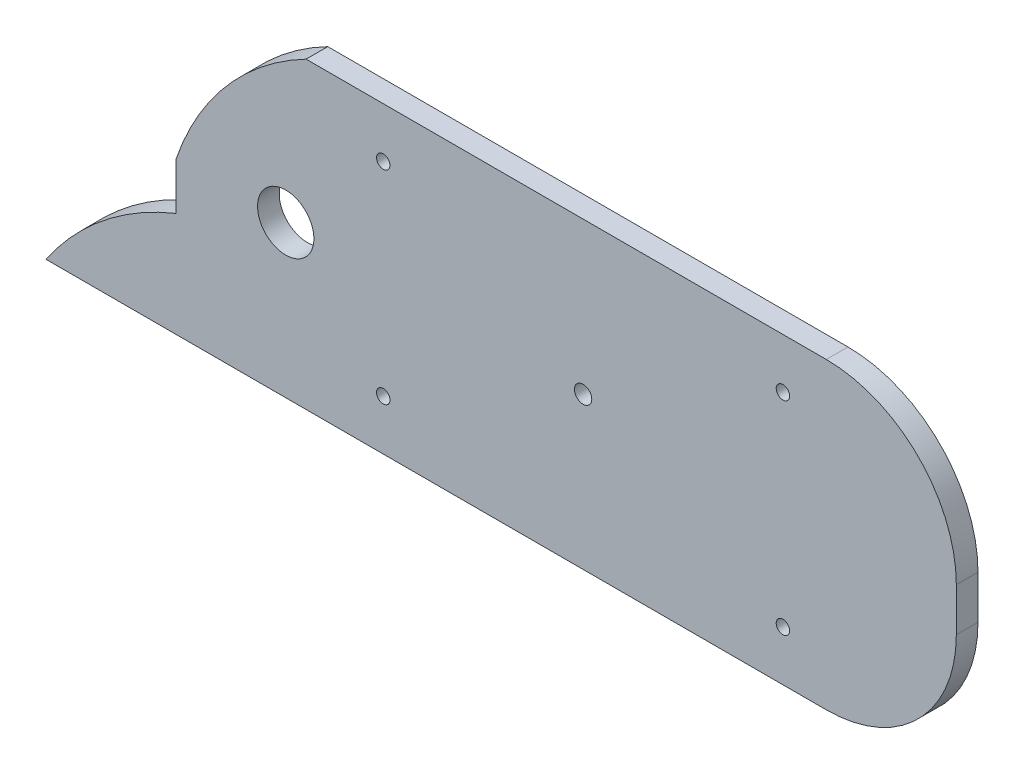
SolidWorks part; units mm, degrees
material "1060 Alloy"
ref_plane "Front Plane" through (0, 0, 0) normal (0, 0, 1) x (1, 0, 0)
ref_plane "Top Plane" through (0, 0, 0) normal (0, 1, 0) x (1, 0, 0)
ref_plane "Right Plane" through (0, 0, 0) normal (1, 0, 0) x (0, 0, -1)
sketch "Sketch2" plane through (0, 0, 0) normal (0, 0, 1) x (1, 0, 0)
  line L0 (0, 0) -> (457.2, 0)
  line L1 (76.2, 0) -> (76.2, 88.9) construction
  line L2 (152.4, 0) -> (152.4, 177.8) construction
  line L9 (457.2, 177.8) -> (152.4, 177.8)
  line L14 (533.4, 76.2) -> (533.4, 101.6)
  line L16 (76.2, 88.9) -> (76.2, 61.4013)
  arc A5 (0, 0) -> (76.2, 61.4013) centre (138.3869, -93.7571) cw
  arc A6 (457.2, 0) -> (533.4, 76.2) centre (457.2, 76.2) ccw
  arc A7 (533.4, 101.6) -> (457.2, 177.8) centre (457.2, 101.6) ccw
  arc A8 (76.2, 88.9) -> (152.4, 177.8) centre (224.2925, 39.0707) cw
  dimension "D6" = 167.1566
  dimension "D7" = 88.9
  dimension "D5" = 177.8
  dimension "D1" = 76.2
  dimension "D4" = 457.2
  dimension "D9" = 138.3869
  dimension "D8" = 156.2509
  dimension "D2" = 76.2
  dimension "D3" = 152.4
extrude "Boss-Extrude1" add sketch "Sketch2" along normal blind 12.7
sketch "Sketch4" plane through (0, 0, 12.7) normal (0, 0, 1) x (1, 0, 0)
  line L0 (314.706, 0) -> (314.706, 177.8) construction
  line L1 (0, 0) -> (457.2, 0) construction
  line L2 (457.2, 177.8) -> (152.4, 177.8) construction
  line L3 (76.2, 88.9) -> (533.4, 88.9) construction
  line L4 (76.2, 88.9) -> (76.2, 61.4013) construction
  line L6 (533.4, 76.2) -> (533.4, 101.6) construction
  circle A0 centre (314.706, 88.9) radius 5.08
  circle A3 centre (431.8, 148.4376) radius 3.937
  circle A4 centre (140.4683, 88.9) radius 16.51
  circle A5 centre (197.612, 148.4376) radius 3.937
  circle A6 centre (197.612, 29.3624) radius 3.937
  circle A7 centre (431.8, 29.3624) radius 3.937
  dimension "D1" = 10.16
  dimension "D4" = 7.874
  dimension "D5" = 29.3624
  dimension "D6" = 117.094
  dimension "D7" = 33.02
  dimension "D2" = 314.706
  dimension "D3" = 88.9
extrude "Cut-Extrude2" cut sketch "Sketch4" against normal through all
equation "\"0.5n\"=0.25"
equation "\".5n\"=0.25"
